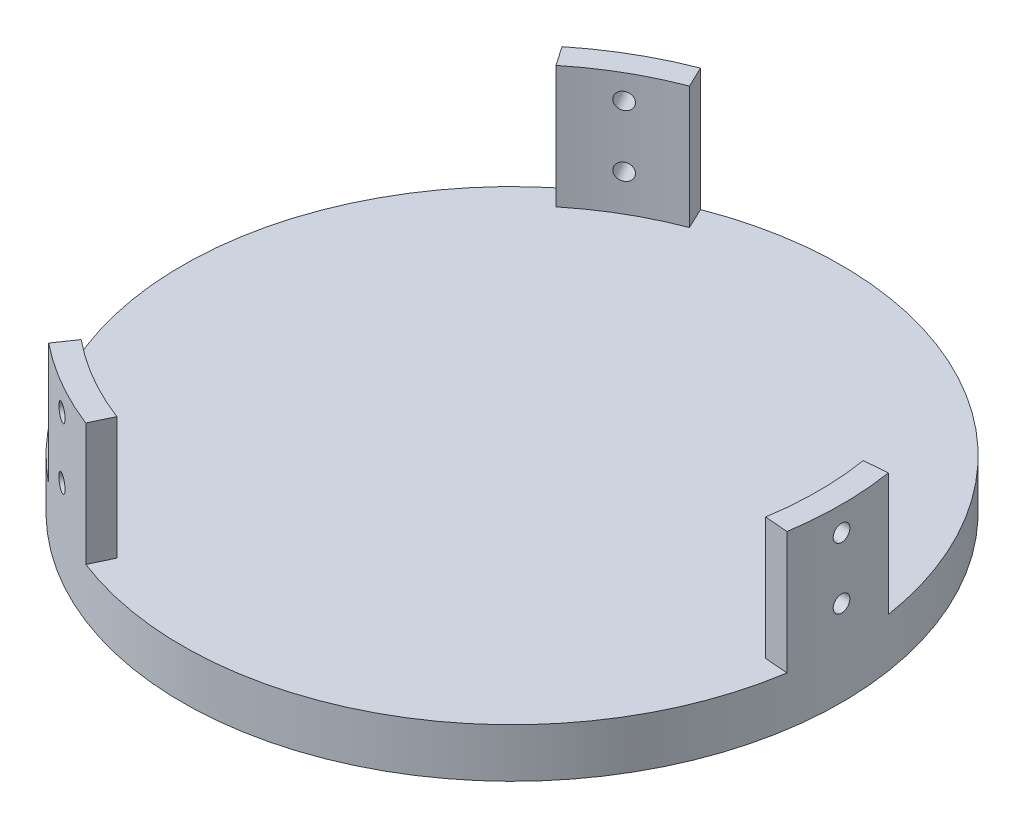
SolidWorks part; units mm, degrees
material "6061-T6 (SS)"
ref_plane "Front" through (0, 0, 0) normal (0, 0, 1) x (1, 0, 0)
ref_plane "Top" through (0, 0, 0) normal (0, 1, 0) x (1, 0, 0)
ref_plane "Right" through (0, 0, 0) normal (1, 0, 0) x (0, 0, -1)
sketch "Sketch1" plane through (0, 0, 0) normal (0, 1, 0) x (1, 0, 0)
  line L1 (0, 0) -> (127.635, 0)
  line L2 (0, 0) -> (0, 127.635)
  line L3 (0, 127.635) -> (127.635, 127.635)
  line L4 (127.635, 0) -> (127.635, 127.635)
  dimension "D1" = 127.635
  dimension "D2" = 127.635
extrude "Main Plate" add sketch "Sketch1" along normal blind 12.7
sketch "Sketch9" plane through (0, 12.7, 0) normal (0, 1, 0) x (1, 0, 0)
  circle A0 centre (63.8175, 63.8175) radius 85.725
  dimension "D1" = 171.45
extrude "Boss-Extrude1" add sketch "Sketch9" against normal up to surface (12.7 mm away) contours A0 up to face at (63.8175, 0, -63.8175)
sketch "Sketch10" plane through (0, 12.7, 0) normal (0, 1, 0) x (1, 0, 0)
  circle A0 centre (63.8175, 63.8175) radius 95.25
  circle A1 centre (63.8175, 63.8175) radius 85.4075
  dimension "D1" = 170.815
  dimension "D2" = 190.5
extrude "Cut-Extrude1" cut sketch "Sketch10" against normal blind 167.64 contours A0 | A1
sketch "Sketch14" plane through (0, 12.7, 0) normal (0, 1, 0) x (1, 0, 0)
  line L0 (201.1692, 63.8175) -> (-73.4523, 63.8175) construction
ref_plane "Plane1" through (0, 0, -63.8175) normal (0, 0, -1) x (-1, 0, 0)
ref_plane "Plane3" through (0, 6.35, 0) normal (0, 1, 0) x (1, 0, 0)
ref_plane "Plane2" through (-21.59, 0, 0) normal (-1, 0, 0) x (0, 0, 1)
sketch "Sketch18" plane through (0, 6.35, 0) normal (0, 1, 0) x (1, 0, 0)
  circle A0 centre (63.8175, 63.8175) radius 85.4075
  circle A1 centre (63.8175, 63.8175) radius 79.375
  circle A4 centre (63.8175, 63.8175) radius 85.4075 construction
  dimension "D1" = 158.75
extrude "Boss-Extrude2" add sketch "Sketch18" along normal blind 38.1
sketch "Sketch20" plane through (0, 12.7, 0) normal (0, 1, 0) x (1, 0, 0)
  line L0 (63.8175, 143.1925) -> (63.8175, -15.5575) construction
  line L1 (-15.5575, 63.8175) -> (143.1925, 63.8175) construction
  line L2 (63.8175, 63.8175) -> (-15.5575, -73.664) construction
  circle A0 centre (63.8175, 63.8175) radius 79.375 construction
  dimension "D1" = 30
ref_plane "Plane5" through (-15.5575, 12.7, 73.664) normal (-0.5, 0, 0.866) x (0.866, 0, 0.5)
sketch "Sketch15" plane through (166.2216, 0, 178.6143) normal (0.5, 0, -0.866) x (-0.866, 0, -0.5)
  line L3 (289.2754, 44.45) -> (130.5254, 44.45) construction
  circle A0 centre (209.9004, 22.225) radius 2.159
  circle A1 centre (209.9004, 38.1) radius 2.159
  dimension "D1" = 4.318
  dimension "D2" = 15.875
  dimension "D3" = 4.318
  dimension "D6" = 6.35
extrude "Cut-Extrude3" cut sketch "Sketch15" along normal blind 88.9
pattern_circular "CirPattern1" count 3 over 360 about axis through (63.8175, -154.94, -63.8175) along (0, 1, 0) of "Cut-Extrude3" reverse direction yes
ref_plane "Plane4" through (63.8175, 0, 0) normal (-1, 0, 0) x (0, 0, 1)
sketch "Sketch23" plane through (0, 12.7, 0) normal (0, 1, 0) x (1, 0, 0)
  line L0 (13.6787, 125.352) -> (7.5523, 134.2379)
  line L1 (15.1867, 11.8815) -> (13.6787, 2.283) construction
  line L3 (-15.5575, 63.8175) -> (143.1925, 63.8175) construction
  line L4 (63.8175, 143.1925) -> (63.8175, -15.5575) construction
  line L5 (-15.5575, 63.8175) -> (143.1925, 63.8175)
  line L6 (63.8175, 143.1925) -> (63.8175, -15.5575)
  line L7 (13.6787, 2.283) -> (6.9592, -7.4631)
  line L8 (-19.2671, 125.3206) -> (-48.797, 60.3978)
  line L9 (-48.797, 60.3978) -> (-9.8843, 7.0525)
  line L10 (-9.8843, 7.0525) -> (6.9592, -7.4631)
  line L11 (24.1345, -4.9259) -> (13.6787, 2.283) construction
  line L14 (7.5523, 134.2379) -> (-19.2671, 125.3206)
  line L15 (24.1345, 132.5609) -> (13.6787, 125.352) construction
  line L28 (63.8175, 63.8175) -> (24.1345, -4.9259) construction
  line L29 (63.8175, 63.8175) -> (24.1345, 132.5609) construction
  line L30 (142.1773, 76.4717) -> (152.9359, 77.3344)
  line L31 (152.9359, 77.3344) -> (158.6231, 105.0193)
  line L32 (158.6231, 105.0193) -> (117.1632, 163.0543)
  line L33 (117.1632, 163.0543) -> (51.5085, 156.0277)
  line L34 (51.5085, 156.0277) -> (30.5159, 148.6985)
  line L35 (35.5964, 138.0062) -> (30.5159, 148.6985)
  line L36 (35.5964, -10.3712) -> (30.9643, -20.1198)
  line L37 (30.9643, -20.1198) -> (52.0965, -38.8874)
  line L38 (52.0965, -38.8874) -> (123.0863, -31.9996)
  line L39 (123.0863, -31.9996) -> (149.8284, 28.3723)
  line L40 (149.8284, 28.3723) -> (153.9775, 50.217)
  line L41 (142.1773, 51.1633) -> (153.9775, 50.217)
  circle A0 centre (63.8175, 63.8175) radius 79.375 construction
  arc A1 (13.6787, 2.283) -> (13.6787, 125.352) centre (63.8175, 63.8175) cw
  circle A3 centre (63.8175, 63.8175) radius 79.375
  arc A6 (35.5964, 138.0062) -> (142.1773, 76.4717) centre (63.8175, 63.8175) cw
  arc A7 (142.1773, 51.1633) -> (35.5964, -10.3712) centre (63.8175, 63.8175) cw
  circle A9 centre (63.8175, 63.8175) radius 79.375
  circle M15 centre (63.8175, 63.8175) radius 79.375
  dimension "D1" = 79.375
  dimension "D2" = 0
  dimension "D3" = 12.7
  dimension "D4" = 90
  dimension "D5" = 12.7
  dimension "D6" = 90
  dimension "D8" = 60.004
  dimension "D9" = 60.004
  dimension "D7" = 3
extrude "Cut-Extrude6" cut sketch "Sketch23" along normal blind 111.6 contours L9 L10 L7 L8 M15 | L34 L35 A6 L30 L31 L32 L33 | L40 L41 A7 L36 L37 L38 L39 region at (-18.2379, 12.7, -69.3048)
